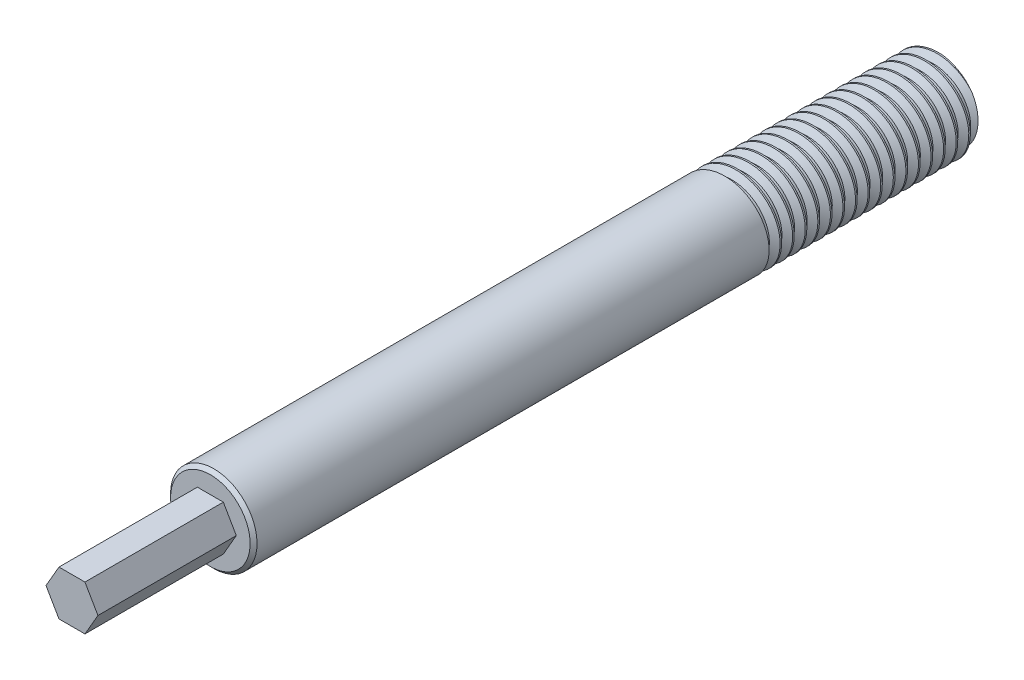
SolidWorks part; units mm, degrees
material "Cast Carbon Steel"
ref_plane "Front Plane" through (0, 0, 0) normal (0, 0, 1) x (1, 0, 0)
ref_plane "Top Plane" through (0, 0, 0) normal (0, 1, 0) x (1, 0, 0)
ref_plane "Right Plane" through (0, 0, 0) normal (1, 0, 0) x (0, 0, -1)
sketch "Sketch1" plane through (0, 0, 0) normal (0, 0, 1) x (1, 0, 0)
  line L1 (4.766, 0) -> (2.383, 4.1275)
  line L2 (2.383, 4.1275) -> (-2.383, 4.1275)
  line L3 (-2.383, 4.1275) -> (-4.766, 0)
  line L4 (-4.766, 0) -> (-2.383, -4.1275)
  line L5 (-2.383, -4.1275) -> (2.383, -4.1275)
  line L6 (2.383, -4.1275) -> (4.766, 0)
  circle A0 centre (0, 0) radius 4.1275 construction
  dimension "D1" = 8.255
extrude "Boss-Extrude1" add sketch "Sketch1" against normal blind 25.4
sketch "Sketch2" plane through (0, 0, -25.4) normal (0, 0, -1) x (-1, 0, 0)
  circle A0 centre (0, 0) radius 7.9375
  dimension "D1" = 15.875
extrude "Boss-Extrude2" add sketch "Sketch2" along normal blind 133.35
chamfer "Chamfer1" distance 0.635 angle 45 1 edges at (-7.9375, 0, -25.4)
thread "Thread1" pitch 2.3091 method cut profile "Thread Profile1" start angle 0, offset 2.54, length 40.64, pitch 2.3091, diameter 15.875
ref_plane "Plane1" through (7.9375, 0, -161.29) normal (0, -1, 0) x (1, 0, 0)
sketch "Thread Profile1" plane through (7.9375, 0, -161.29) normal (0, -1, 0) x (1, 0, 0)
  line L0 (0, 0) -> (0, 2.3091) construction
  line L11 (0, 0) -> (0, 2.0205)
  line L12 (0, 2.0205) -> (-1.2498, 1.2989)
  line L13 (-1.2498, 1.2989) -> (-1.2498, 0.7216)
  line L15 (-1.2498, 0.7216) -> (0, 0)
  line L17 (-1.2498, 1.0102) -> (0, 1.0102) construction
  point P2 (0, 0)
  dimension "Pitch" = 2.3091
  dimension "Profile_Angle" = 60
  dimension "Profile_Land" = 0.5773
  dimension "Profile_Height" = 1.2498
